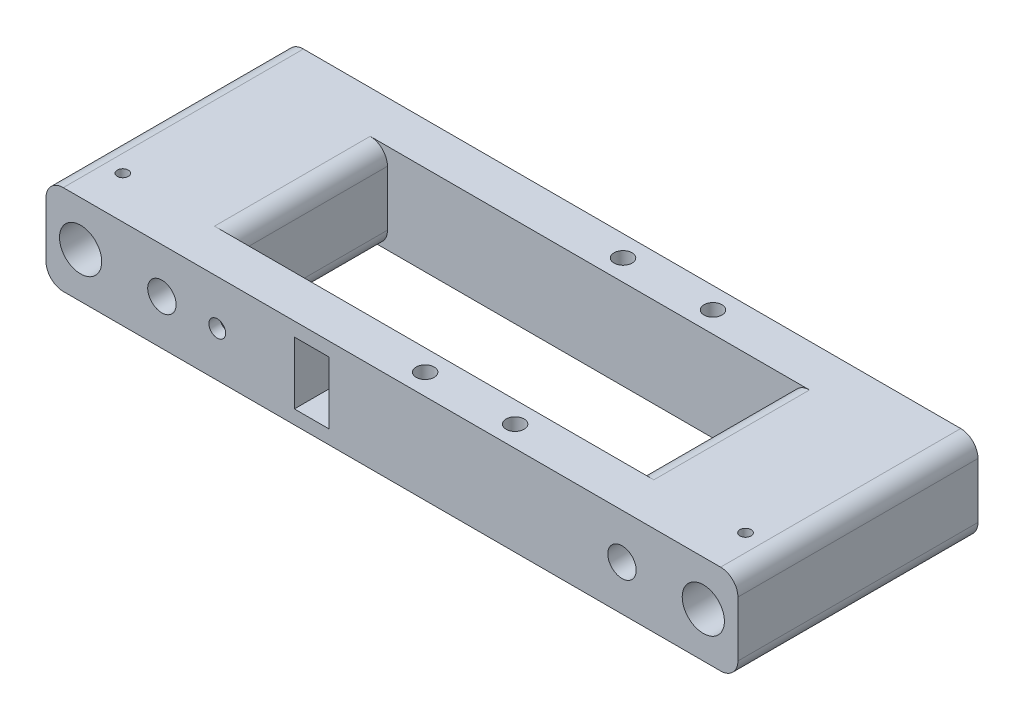
SolidWorks part; units mm, degrees
ref_plane "Front Plane" through (0, 0, 0) normal (0, 0, 1) x (1, 0, 0)
ref_plane "Top Plane" through (0, 0, 0) normal (0, 1, 0) x (1, 0, 0)
ref_plane "Right Plane" through (0, 0, 0) normal (1, 0, 0) x (0, 0, -1)
sketch "Sketch1" plane through (0, 0, 0) normal (0, 0, 1) x (1, 0, 0)
  line L0 (-58.5, 26) -> (-58.5, 0) construction
  line L1 (0, 0) -> (-100, 0)
  line L2 (0, 0) -> (0, 26)
  line L3 (0, 26) -> (-100, 26)
  line L4 (-100, 0) -> (-100, 26)
  circle A0 centre (-90, 13) radius 6.1
  circle A1 centre (-66.5, 13) radius 4.1
  point P9 (-100, 13)
  dimension "D3" = 12.2
  dimension "D4" = 8.2
  dimension "D1" = 100
  dimension "D2" = 26
  dimension "D5" = 23.5
  dimension "D6" = 10
  dimension "D7" = 8
  dimension "D8" = 41.5
extrude "Boss-Extrude1" add sketch "Sketch1" along normal blind 40
sketch "Sketch2" plane through (0, 0, 0) normal (0, 0, -1) x (-1, 0, 0)
  line L1 (100, 26) -> (0, 26)
  line L2 (100, 26) -> (100, 0)
  line L3 (100, 0) -> (0, 0)
  line L4 (0, 26) -> (0, 0)
extrude "Boss-Extrude2" add sketch "Sketch2" along normal blind 29.4
sketch "Sketch3" plane through (0, 26, 0) normal (0, 1, 0) x (1, 0, 0)
  line L0 (0, -40) -> (0, 29.4) construction
  line L1 (0, 17.2) -> (-58.5, 17.2)
  line L2 (0, 17.2) -> (0, -27.8)
  line L3 (0, -27.8) -> (-58.5, -27.8)
  line L4 (-58.5, 17.2) -> (-58.5, -27.8)
  line L5 (-100, -40) -> (-100, 29.4) construction
  line L6 (-100, 29.4) -> (0, 29.4) construction
  line L7 (0, -40) -> (-100, -40) construction
  dimension "D1" = 41.5
  dimension "D2" = 12.2
  dimension "D3" = 12.2
extrude "Cut-Extrude1" cut sketch "Sketch3" against normal up to next
mirror "Mirror2" about plane through (0, 0, 40) normal (-1, 0, 0) of "Boss-Extrude2", "Cut-Extrude1", "Boss-Extrude1"
sketch "Sketch4" plane through (0, 26, 0) normal (0, 1, 0) x (1, 0, 0)
  line L0 (-100, 29.4) -> (100, 29.4) construction
  line L1 (-5.5, 29.4) -> (-5.5, 17.2) construction
  line L2 (58.5, 17.2) -> (-58.5, 17.2) construction
  line L3 (58.5, 17.2) -> (58.5, -27.8) construction
  circle A0 centre (3.5, 23.3) radius 2.6
  circle A1 centre (29.5, 23.3) radius 2.6
  dimension "D1" = 6.1
  dimension "D3" = 9
  dimension "D4" = 26
  dimension "D5" = 5.2
  dimension "D2" = 64
extrude "Cut-Extrude2" cut sketch "Sketch4" against normal through all
sketch "Sketch5" plane through (0, 0, 0) normal (0, -1, 0) x (1, 0, 0)
  line L1 (34.2343, -23.3) -> (31.8671, -19.2)
  line L2 (31.8671, -19.2) -> (27.1329, -19.2)
  line L3 (27.1329, -19.2) -> (24.7657, -23.3)
  line L4 (24.7657, -23.3) -> (27.1329, -27.4)
  line L5 (27.1329, -27.4) -> (31.8671, -27.4)
  line L6 (31.8671, -27.4) -> (34.2343, -23.3)
  line L7 (-1.2343, -23.3) -> (1.1329, -27.4)
  line L8 (1.1329, -27.4) -> (5.8671, -27.4)
  line L9 (5.8671, -27.4) -> (8.2343, -23.3)
  line L10 (8.2343, -23.3) -> (5.8671, -19.2)
  line L11 (5.8671, -19.2) -> (1.1329, -19.2)
  line L12 (1.1329, -19.2) -> (-1.2343, -23.3)
  circle A0 centre (29.5, -23.3) radius 4.1 construction
  circle A1 centre (3.5, -23.3) radius 4.1 construction
  dimension "D1" = 8.2
  dimension "D2" = 8.2
extrude "Cut-Extrude3" cut sketch "Sketch5" against normal blind 4
ref_plane "Plane1" through (0, 0, 5.3) normal (0, 0, 1) x (1, 0, 0)
mirror "Mirror3" about plane through (0, 0, 5.3) normal (0, 0, 1) of "Cut-Extrude3", "Cut-Extrude2"
sketch "Sketch6" plane through (0, 0, 40) normal (0, 0, 1) x (1, 0, 0)
  line L0 (-8.1, 26) -> (-8.1, 0) construction
  line L1 (100, 26) -> (-100, 26) construction
  line L2 (-100, 0) -> (100, 0) construction
  line L3 (0.9, 26) -> (0.9, 4) construction
  line L4 (-100, 26) -> (-100, 0) construction
  line L5 (-18.2, 22) -> (-28.2, 22)
  line L6 (-18.2, 22) -> (-18.2, 4)
  line L7 (-18.2, 4) -> (-28.2, 4)
  line L8 (-28.2, 22) -> (-28.2, 4)
  point P12 (-28.2, 13)
  point P15 (-100, 13)
  dimension "D1" = 9
  dimension "D2" = 10.1
  dimension "D3" = 10
  dimension "D4" = 18
extrude "Cut-Extrude4" cut sketch "Sketch6" against normal up to vertex (14 mm away) up to point (0, -58.5, 26)
fillet "Fillet1" radius 5 8 edges at (58.5, 0, 5.3) (-58.5, 0, 5.3) (58.5, 26, 5.3) (100, 0, 5.3) (100, 26, 5.3) (-100, 0, 5.3) (-100, 26, 5.3) (-58.5, 26, 5.3)
sketch "Sketch7" plane through (0, 0, 27.8) normal (0, 0, -1) x (-1, 0, 0)
  line L0 (58.5, 5) -> (58.5, 21) construction
  circle A0 centre (50.5, 13) radius 5
  point P4 (58.5, 13)
  dimension "D1" = 10
  dimension "D2" = 8
extrude "Cut-Extrude5" cut sketch "Sketch7" against normal blind 9 contours A0
sketch "Sketch8" plane through (0, 0, 36.8) normal (0, 0, -1) x (-1, 0, 0)
  circle A0 centre (50.5, 13) radius 2.4278
extrude "Cut-Extrude6" cut sketch "Sketch8" against normal up to next
sketch "Sketch9" plane through (0, 26, 0) normal (0, 1, 0) x (1, 0, 0)
  line L0 (83.9, -40) -> (96.1, -40) construction
  line L1 (-96.1, -40) -> (-83.9, -40) construction
  line L2 (83.9, -40) -> (96.1, -40) construction
  line L3 (-96.1, -40) -> (-83.9, -40) construction
  line L4 (95, -40) -> (-95, -40) construction
  circle A0 centre (-90, -27.8) radius 1.6
  circle A1 centre (90, -27.8) radius 1.6
  point P10 (0, 0)
  point P11 (0, 0)
  point P12 (90, -40)
  point P13 (0, 0)
  point P14 (-90, -40)
  dimension "D2" = 3.2
  dimension "D3" = 3.2
  dimension "D1" = 12.2
extrude "Cut-Extrude7" cut sketch "Sketch9" against normal through all and the other way through all
sketch "Sketch10" plane through (0, 0, 0) normal (0, -1, 0) x (1, 0, 0)
  line L1 (-90, 31.0909) -> (-92.85, 29.4454)
  line L2 (-92.85, 29.4454) -> (-92.85, 26.1546)
  line L3 (-92.85, 26.1546) -> (-90, 24.5091)
  line L4 (-90, 24.5091) -> (-87.15, 26.1546)
  line L5 (-87.15, 26.1546) -> (-87.15, 29.4454)
  line L6 (-87.15, 29.4454) -> (-90, 31.0909)
  line L7 (90, 31.0909) -> (87.15, 29.4454)
  line L8 (87.15, 29.4454) -> (87.15, 26.1546)
  line L9 (87.15, 26.1546) -> (90, 24.5091)
  line L10 (90, 24.5091) -> (92.85, 26.1546)
  line L11 (92.85, 26.1546) -> (92.85, 29.4454)
  line L12 (92.85, 29.4454) -> (90, 31.0909)
  circle A0 centre (-90, 27.8) radius 2.85 construction
  circle A1 centre (90, 27.8) radius 2.85 construction
  point P10 (0, 0)
  point P19 (0, 0)
  dimension "D1" = 5.7
  dimension "D2" = 5.7
extrude "Cut-Extrude8" cut sketch "Sketch10" against normal blind 3
